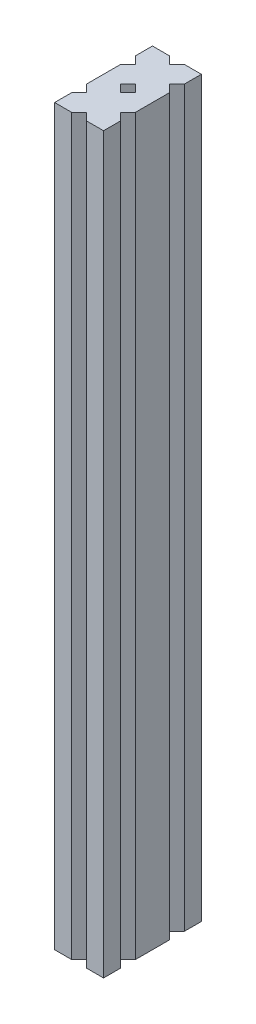
SolidWorks part; units mm, degrees
ref_plane "Front" through (0, 0, 0) normal (0, 0, 1) x (1, 0, 0)
ref_plane "Top" through (0, 0, 0) normal (0, 1, 0) x (1, 0, 0)
ref_plane "Right" through (0, 0, 0) normal (1, 0, 0) x (0, 0, -1)
sketch "Skizze1" plane through (0, 0, 0) normal (0, 1, 0) x (1, 0, 0)
  line L0 (0, 0) -> (0, 40)
  line L1 (0, 40) -> (20, 40)
  line L2 (20, 40) -> (20, 0)
  line L3 (20, 0) -> (0, 0)
  dimension "D1" = 20
  dimension "D2" = 40
extrude "Aufsatz-Linear austragen1" add sketch "Skizze1" along normal blind 300
sketch "Skizze2" plane through (0, 300, 0) normal (0, 1, 0) x (1, 0, 0)
  line L0 (10, 40) -> (10, 20) construction
  line L1 (0, 30) -> (20, 30) construction
  line L2 (7, 40) -> (10, 37)
  line L3 (13, 40) -> (10, 37)
  line L4 (10, 30) -> (20, 40) construction
  line L5 (7, 40) -> (13, 40)
  line L6 (20, 33) -> (17, 30)
  line L7 (20, 27) -> (17, 30)
  line L8 (20, 27) -> (20, 33)
  line L9 (0, 27) -> (0, 33)
  line L10 (0, 27) -> (3, 30)
  line L11 (0, 33) -> (3, 30)
  line L12 (7, 20) -> (13, 20)
  line L13 (13, 20) -> (10, 23)
  line L14 (7, 20) -> (10, 23)
  line L15 (0, 20) -> (20, 20) construction
  line L16 (0, 40) -> (0, 0) construction
  line L17 (20, 0) -> (20, 40) construction
  line L18 (20, 40) -> (0, 40) construction
  line L19 (7, 20) -> (10, 17)
  line L20 (13, 20) -> (10, 17)
  line L21 (20, 13) -> (17, 10)
  line L22 (20, 7) -> (17, 10)
  line L23 (20, 13) -> (20, 7)
  line L24 (13, 0) -> (10, 3)
  line L25 (7, 0) -> (13, 0)
  line L26 (7, 0) -> (10, 3)
  line L27 (0, 13) -> (3, 10)
  line L28 (0, 13) -> (0, 7)
  line L29 (0, 7) -> (3, 10)
  line M14 (0, 0) -> (20, 0)
  line M15 (20, 0) -> (20, 40)
  line M16 (20, 40) -> (0, 40)
  line M17 (0, 40) -> (0, 0)
  dimension "D1" = 3
  dimension "D2" = 3
extrude "Schnitt-Linear austragen1" cut sketch "Skizze2" against normal through all contours L11 L10 M17 | L3 L2 M16 | L7 L6 M15 | L20 L12 L19 | L14 L12 L13 | L22 L21 M15 | L29 L27 M17 | L26 L24 M14 region at (10, 300, -39) region at (1, 300, -30) region at (19, 300, -30) region at (1, 300, -10) region at (19, 300, -10) region at (10, 300, -1) region at (10, 300, -21) region at (10, 300, -19)
ref_plane "Ebene1" through (0, 150, 0) normal (0, 1, 0) x (1, 0, 0)
